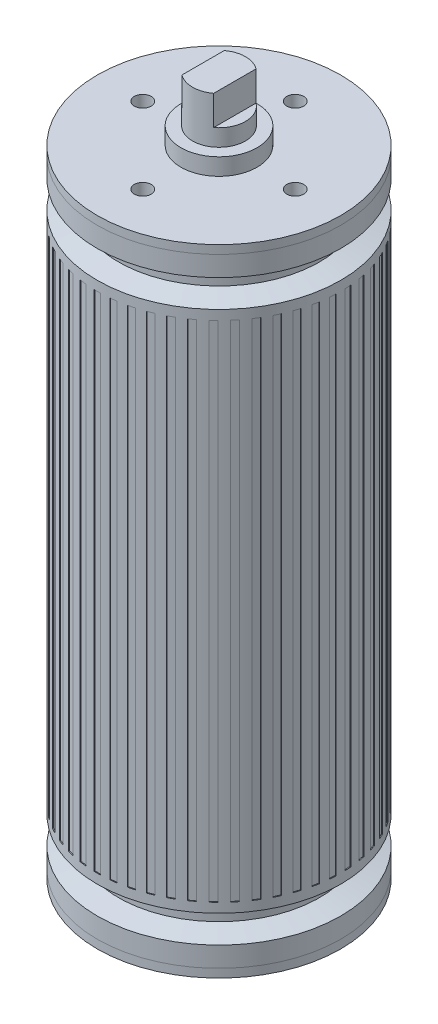
SolidWorks part; units mm, degrees
ref_plane "Ön Düzlem" through (0, 0, 0) normal (0, 0, 1) x (1, 0, 0)
ref_plane "Üst Düzlem" through (0, 0, 0) normal (0, 1, 0) x (1, 0, 0)
ref_plane "Sağ Düzlem" through (0, 0, 0) normal (1, 0, 0) x (0, 0, -1)
sketch "Sketch1" plane through (0, 0, 0) normal (0, 0, 1) x (1, 0, 0)
  line L0 (0, 0) -> (0, 360)
  line L1 (0, 0) -> (12.5, 0)
  line L2 (12.5, 0) -> (12.5, 22)
  line L3 (18, 30) -> (57.5, 30)
  line L4 (57.5, 30) -> (57.5, 330)
  line L5 (57.5, 330) -> (18, 330)
  line L6 (12.5, 360) -> (12.5, 338)
  line L7 (12.5, 360) -> (0, 360)
  line L8 (12.5, 22) -> (18, 22)
  line L9 (18, 22) -> (18, 30)
  line L10 (12.5, 338) -> (18, 338)
  line L11 (18, 338) -> (18, 330)
  line L12 (0, 180) -> (57.5, 180) construction
  line L13 (47.5, 54) -> (57.5, 56.5)
  line L14 (47.5, 54) -> (47.5, 46)
  line L15 (47.5, 46) -> (57.5, 43.5)
  line L16 (47.5, 50) -> (57.5, 50) construction
  line L17 (47.5, 54) -> (57.5, 56.5)
  line L18 (47.5, 46) -> (57.5, 43.5)
  line L19 (47.5, 310) -> (57.5, 310) construction
  line L20 (47.5, 314) -> (57.5, 316.5)
  line L21 (47.5, 306) -> (57.5, 303.5)
  line L22 (47.5, 314) -> (57.5, 316.5)
  line L23 (47.5, 306) -> (57.5, 303.5)
  line L24 (47.5, 306) -> (47.5, 314)
  dimension "D1" = 12.5
  dimension "D2" = 30
  dimension "D3" = 18
  dimension "D4" = 8
  dimension "D5" = 300
  dimension "D6" = 57.5
  dimension "D7" = 8
  dimension "D8" = 13
  dimension "D9" = 10
  dimension "D10" = 20
revolve "Revolve1" add sketch "Sketch1" angle 360 about L0 region at (27.456, 180, 0)
ref_axis "Axis1" through (0, 303.5, 0) along (0, -1, 0)
ref_plane "Plane1" through (0, 54, 0) normal (0, 1, 0) x (1, 0, 0)
ref_plane "Plane2" through (0, 306, 0) normal (0, -1, 0) x (-1, 0, 0)
ref_plane "Plane3" through (0, 61, 0) normal (0, 1, 0) x (1, 0, 0)
ref_plane "Plane4" through (0, 299, 0) normal (0, -1, 0) x (-1, 0, 0)
sketch "Sketch3" plane through (0, 61, 0) normal (0, 1, 0) x (1, 0, 0)
  line L1 (1.5, 57.1) -> (-1.5, 57.1)
  line L2 (1.5, 57.1) -> (1.5, 57.9)
  line L3 (1.5, 57.9) -> (-1.5, 57.9)
  line L4 (-1.5, 57.1) -> (-1.5, 57.9)
  line L5 (1.5, 57.1) -> (-1.5, 57.9) construction
  line L6 (1.5, 57.9) -> (-1.5, 57.1) construction
  circle A0 centre (0, 0) radius 57.5 construction
  point P0 (0, 57.5)
  dimension "D1" = 3
  dimension "D2" = 0.8
extrude "Cut-Extrude2" cut sketch "Sketch3" along normal up to surface (238 mm away) up to plane "Plane4"
pattern_circular "CirPattern1" count 50 over 360 about axis through (0, 43.5, 0) along (0, -1, 0) of "Cut-Extrude2"
ref_plane "Plane5" through (0, 180, 0) normal (0, 1, 0) x (1, 0, 0)
sketch "Sketch4" plane through (0, 30, 0) normal (0, -1, 0) x (1, 0, 0)
  circle A0 centre (0, 36) radius 4
  circle A1 centre (36, 0) radius 4
  circle A2 centre (0, -36) radius 4
  circle A3 centre (-36, 0) radius 4
  point P12 (0, 0)
  dimension "D1" = 8
  dimension "D2" = 36
  dimension "D3" = 4
extrude "Cut-Extrude3" cut sketch "Sketch4" against normal blind 50
sketch "Sketch5" plane through (0, 0, 0) normal (0, 0, 1) x (1, 0, 0)
  line L0 (-7.5, 14) -> (-22.5067, 14)
  line L1 (7.5, -14) -> (-7.5, -14)
  line L2 (7.5, -14) -> (7.5, 14)
  line L3 (7.5, 14) -> (-7.5, 14)
  line L4 (-7.5, -14) -> (-7.5, 14)
  line L5 (7.5, -14) -> (-7.5, 14) construction
  line L6 (7.5, 14) -> (-7.5, -14) construction
  line L7 (-22.5067, 14) -> (-22.5067, 0)
  line L8 (-22.5067, 0) -> (-7.5, 0)
  line L9 (7.5, 0) -> (20.8508, 0)
  line L10 (20.8508, 0) -> (20.8508, 14)
  line L11 (20.8508, 14) -> (7.5, 14)
  point P0 (0, 0)
  dimension "D1" = 15
  dimension "D2" = 28
extrude "Cut-Extrude4" cut sketch "Sketch5" against normal mid plane 40 contours L10 L11 L2 L9 | L7 L8 L4 L0 region at (-15.0033, 7, 0) region at (14.1754, 7, 0)
mirror "Mirror1" about plane through (0, 180, 0) normal (0, 1, 0) of "Cut-Extrude3", "Cut-Extrude4"
ref_plane "Plane6" through (0, 34, 0) normal (0, -1, 0) x (-1, 0, 0)
ref_plane "Plane7" through (0, 326, 0) normal (0, 1, 0) x (1, 0, 0)
split line "Split Line1"
split line "Split Line2"
